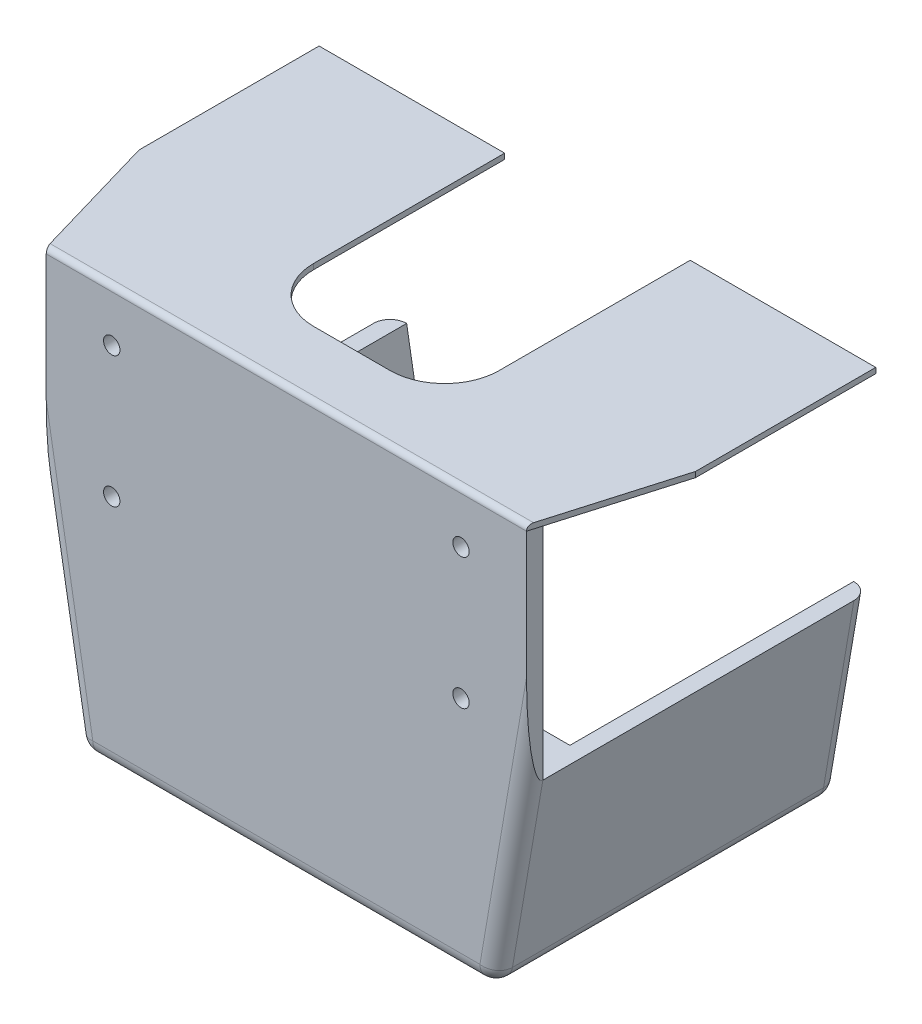
SolidWorks part; units mm, degrees
ref_plane "Front Plane" through (0, 0, 0) normal (0, 0, 1) x (1, 0, 0)
ref_plane "Top Plane" through (0, 0, 0) normal (0, 1, 0) x (1, 0, 0)
ref_plane "Right Plane" through (0, 0, 0) normal (1, 0, 0) x (0, 0, -1)
sketch "Sketch1" plane through (0, 0, 0) normal (0, 0, 1) x (1, 0, 0)
  line L1 (0, 0) -> (88, 0)
  line L2 (0, 0) -> (0, 41)
  line L3 (0, 41) -> (88, 41)
  line L4 (88, 0) -> (88, 41)
  dimension "D1" = 88
  dimension "D2" = 41
extrude "Boss-Extrude1" add sketch "Sketch1" along normal blind 3
sketch "Sketch2" plane through (0, 0, 3) normal (0, 0, 1) x (1, 0, 0)
  line L0 (0, 0) -> (88, 0)
  line L1 (0, 0) -> (6, -35)
  line L3 (88, 0) -> (82, -35)
  line L4 (82, -35) -> (6, -35)
  line L5 (44, 0) -> (44, -52.8386) construction
  line L6 (0, 0) -> (88, 0) construction
  point P12 (44, -35)
  dimension "D1" = 76
  dimension "D2" = 35
extrude "Boss-Extrude2" add sketch "Sketch2" against normal blind 3
sketch "Sketch3" plane through (0, 0, 0) normal (0, 0, -1) x (-1, 0, 0)
  line L0 (-88, 0) -> (0, 0) construction
  line L1 (-44, 0) -> (-44, -35) construction
  line L2 (-6, -35) -> (-82, -35) construction
  line L3 (-82, -35) -> (-88, 0)
  line L4 (-88, 0) -> (-84.9562, 0)
  line L5 (-84.9562, 0) -> (-79.4705, -32)
  line L6 (-79.4705, -32) -> (-60, -32)
  line L7 (-60, -32) -> (-60, -35)
  line L8 (-60, -35) -> (-82, -35)
  line L9 (-28, -35) -> (-6, -35)
  line L10 (-28, -32) -> (-28, -35)
  line L11 (-8.5295, -32) -> (-28, -32)
  line L12 (-3.0438, 0) -> (-8.5295, -32)
  line L13 (0, 0) -> (-3.0438, 0)
  line L14 (-6, -35) -> (0, 0)
  dimension "D1" = 3
  dimension "D2" = 3
  dimension "D3" = 22
extrude "Boss-Extrude3" add sketch "Sketch3" along normal blind 60
sketch "Sketch4" plane through (0, 41, 0) normal (0, 1, 0) x (1, 0, 0)
  line L0 (0, -3) -> (-7, 21)
  line L1 (-7, 21) -> (-7, 54)
  line L2 (-7, 54) -> (27, 54)
  line L3 (27, 54) -> (27, 9)
  line L4 (27, 9) -> (61, 9)
  line L5 (61, 9) -> (61, 54)
  line L6 (61, 54) -> (95, 54)
  line L7 (95, 54) -> (95, 21)
  line L8 (95, 21) -> (88, -3)
  line L9 (88, -3) -> (0, -3)
  line L10 (44, -3) -> (44, 26.0678) construction
  point P14 (44, 9)
  dimension "D1" = 34
  dimension "D2" = 45
  dimension "D3" = 33
  dimension "D4" = 12
  dimension "D5" = 34
  dimension "D6" = 34
extrude "Boss-Extrude4" add sketch "Sketch4" along normal blind 1
fillet "Fillet1" radius 10 2 edges at (61, 41.5, -9) (27, 41.5, -9)
sketch "Sketch5" plane through (0, 0, 0) normal (0, 0, -1) x (-1, 0, 0)
  line L1 (-60, -32) -> (-28, -32)
  line L2 (-60, -32) -> (-60, -35)
  line L3 (-60, -35) -> (-28, -35)
  line L4 (-28, -32) -> (-28, -35)
extrude "Boss-Extrude5" add sketch "Sketch5" along normal blind 8
fillet "Fillet2" radius 10 2 edges at (60, -33.5, -8) (28, -33.5, -8)
fillet "Fillet6" radius 1 1 edges at (44, 42, 3)
fillet "Fillet12" radius 3 11 edges at (85, -17.5, -60) (60, -33.5, -60) (28, -33.5, -60) (3, -17.5, -60) (3, -17.5, 3) (85, -17.5, 3) (71, -35, -60) (17, -35, -60) (82, -35, -28.5) (6, -35, -28.5) (44, -35, 3)
sketch "Sketch6" plane through (0, 0, 0) normal (0, 0, -1) x (-1, 0, 0)
  line L1 (-84.9562, 0) -> (-3.0438, 0)
  line L2 (-84.9562, 0) -> (-84.9562, -4)
  line L3 (-84.9562, -4) -> (-3.0438, -4)
  line L4 (-3.0438, 0) -> (-3.0438, -4)
  dimension "D1" = 4
extrude "Boss-Extrude6" add sketch "Sketch6" along normal blind 8
sketch "Sketch7" plane through (0, 0, 0) normal (0, 0, -1) x (-1, 0, 0)
  line L0 (-88, 20.5) -> (0, 20.5) construction
  line L1 (-88, 0) -> (-88, 41) construction
  line L2 (0, 41) -> (0, 0) construction
  line L3 (-44, 0) -> (-44, 41) construction
  line L4 (-3.0438, 0) -> (-84.9562, 0) construction
  line L5 (-88, 41) -> (0, 41) construction
  circle A0 centre (-12, 32.5) radius 1.5
  circle A1 centre (-76, 32.5) radius 1.5
  circle A2 centre (-76, 8.5) radius 1.5
  circle A3 centre (-12, 8.5) radius 1.5
  dimension "D3" = 3
  dimension "D1" = 32
  dimension "D2" = 12
extrude "Cut-Extrude1" cut sketch "Sketch7" against normal blind 3
